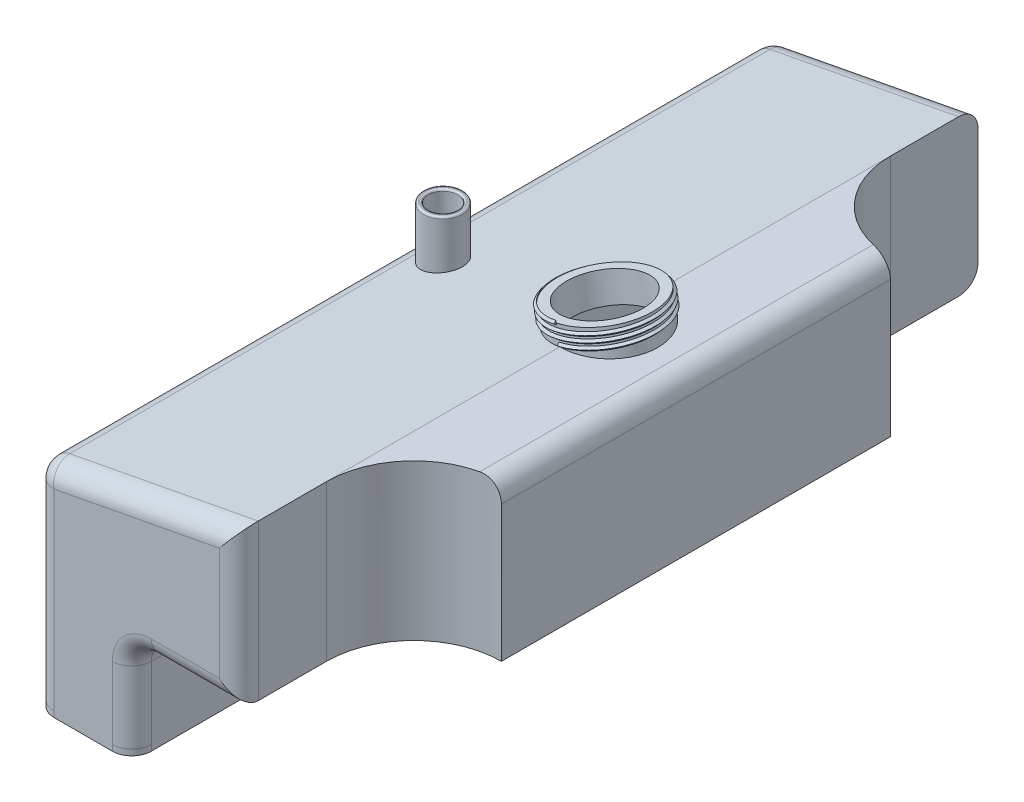
SolidWorks part; units mm, degrees
ref_plane "Front Plane" through (0, 0, 0) normal (0, 0, 1) x (1, 0, 0)
ref_plane "Top Plane" through (0, 0, 0) normal (0, 1, 0) x (1, 0, 0)
ref_plane "Right Plane" through (0, 0, 0) normal (1, 0, 0) x (0, 0, -1)
sketch "Sketch1" plane through (0, 0, 0) normal (0, 1, 0) x (1, 0, 0)
  line L0 (0, 0) -> (0, -145) construction
  line L5 (0, 0) -> (0, 145) construction
  line L6 (0, 100) -> (0, -100)
  line L8 (-150, -145) -> (-150, 145)
  line L12 (-150, 145) -> (-150, 190)
  line L13 (-150, 190) -> (-45, 190)
  line L14 (-45, 145) -> (-45, 190)
  line L16 (-150, -145) -> (-150, -190)
  line L17 (-150, -190) -> (-45, -190)
  line L18 (-45, -145) -> (-45, -190)
  arc A2 (-45, 145) -> (0, 100) centre (0, 145) ccw
  arc A3 (0, -100) -> (-45, -145) centre (0, -145) ccw
extrude "Boss-Extrude4" add sketch "Sketch1" along normal blind 80
sketch "Sketch2" plane through (0, 0, 0) normal (0, -1, 0) x (1, 0, 0)
  line L0 (-45, -190) -> (-150, -190) construction
  line L1 (-150, 190) -> (-100, 190)
  line L2 (-150, 190) -> (-150, -190)
  line L3 (-150, -190) -> (-100, -190)
  line L4 (-100, 190) -> (-100, -190)
extrude "Boss-Extrude5" add sketch "Sketch2" along normal blind 50
sketch "Sketch4" plane through (0, 0, 190) normal (0, 0, 1) x (1, 0, 0)
  line L0 (-45, 80) -> (-45, 60) construction
  line L1 (-45, 80) -> (-45, 0) construction
  line L2 (-45, 60) -> (-150, 60) construction
  line L3 (-150, 80) -> (-150, -50) construction
  line L4 (-150, 60) -> (-45, 80)
  line L5 (-150, 80) -> (-150, 60)
  line L6 (-150, 80) -> (-45, 80)
extrude "Cut-Extrude2" cut sketch "Sketch4" against normal through all
fillet "Fillet1" radius 10 11 edges at (-100, -25, -190) (-72.5, 0, 190) (-150, 5, -190) (-72.5, 0, -190) (-100, -25, 190) (-100, 0, 0) (-150, 5, 190) (-45, 40, 190) (-97.5, 70, -190) (-97.5, 70, 190) (-150, 60, 0)
fillet "Fillet2" radius 10 1 edges at (0, 80, 0)
shell "Shell1" thickness 5 removed face at (-125, -50, 0)
sketch "Sketch5" plane through (0, 0, -185) normal (0, 0, 1) x (1, 0, 0)
  line L0 (-100, -10) -> (-100, -50) construction
  line L1 (-150, -50) -> (-100, -50)
  line L2 (-150, -50) -> (-150, -47)
  line L3 (-150, -47) -> (-100, -47)
  line L4 (-100, -50) -> (-100, -47)
extrude "Boss-Extrude6" add sketch "Sketch5" along normal through all
fillet "Fillet3" radius 10 4 edges at (-150, -48.5, -185) (-100, -48.5, -185) (-100, -48.5, 190) (-150, -48.5, 190)
sketch "Sketch6" plane through (-16.2801, 85.4705, 0) normal (-0.1871, 0.9823, 0) x (0.9823, 0.1871, 0)
  line L0 (-29.2363, -145) -> (-29.2363, 145) construction
  circle A0 centre (-29.2363, 0) radius 20
  circle A1 centre (-29.2363, 0) radius 25
extrude "Boss-Extrude7" add sketch "Sketch6" along normal blind 10 and the other way blind 5
sketch "Sketch7" plane through (-18.1512, 95.2938, 0) normal (-0.1871, 0.9823, 0) x (0.9823, 0.1871, 0)
  line L0 (-29.2363, -20) -> (-29.2363, 20) construction
  circle A0 centre (-29.2363, 0) radius 25
curve "Helix/Spiral1" pitch 3 height 9 radius 25 centre (-46.8711, 89.8234, 0) axis (0.1871, -0.9823, 0) start towards (0, 0, 1)
ref_plane "Plane1" through (-28.7199, -5.4705, 0) normal (0.9823, 0.1871, 0) x (0, 0, -1)
sketch "Sketch8" plane through (-28.7199, -5.4705, 0) normal (0.9823, 0.1871, 0) x (0, 0, -1)
  line L0 (-25, 89.0071) -> (-25, 87.0071)
  line L1 (-25, 97.0071) -> (-25, 87.0071) construction
  line L2 (-25, 87.0071) -> (-26.203, 88.0071)
  line L4 (-25, 89.0071) -> (-26.203, 88.0071)
  spline S0 degree 3 poles (-25, 97.0071) (-25, 96.9618) (-24.3156, 96.8707) (-21.3192, 96.7344) (-16.5956, 96.598) (-10.5275, 96.4617) (-3.6066, 96.3253) (3.6066, 96.1889) (10.5275, 96.0526) (16.5956, 95.9162) (21.3192, 95.7799) (24.3156, 95.6435) (25.3422, 95.5071) (24.3156, 95.3708) (21.3192, 95.2344) (16.5956, 95.098) (10.5275, 94.9617) (3.6066, 94.8253) (-3.6066, 94.6889) (-10.5275, 94.5526) (-16.5956, 94.4162) (-21.3192, 94.2799) (-24.3156, 94.1435) (-25.3422, 94.0071) (-24.3156, 93.8708) (-21.3192, 93.7344) (-16.5956, 93.598) (-10.5275, 93.4617) (-3.6066, 93.3253) (3.6066, 93.1889) (10.5275, 93.0526) (16.5956, 92.9162) (21.3192, 92.7799) (24.3156, 92.6435) (25.3422, 92.5071) (24.3156, 92.3708) (21.3192, 92.2344) (16.5956, 92.098) (10.5275, 91.9617) (3.6066, 91.8253) (-3.6066, 91.6889) (-10.5275, 91.5526) (-16.5956, 91.4162) (-21.3192, 91.2799) (-24.3156, 91.1435) (-25.3422, 91.0071) (-24.3156, 90.8708) (-21.3192, 90.7344) (-16.5956, 90.598) (-10.5275, 90.4617) (-3.6066, 90.3253) (3.6066, 90.1889) (10.5275, 90.0526) (16.5956, 89.9162) (21.3192, 89.7799) (24.3156, 89.6435) (25.3422, 89.5071) (24.3156, 89.3708) (21.3192, 89.2344) (16.5956, 89.098) (10.5275, 88.9617) (3.6066, 88.8253) (-3.6066, 88.6889) (-10.5275, 88.5526) (-16.5956, 88.4162) (-21.3192, 88.2798) (-24.3156, 88.1436) (-25, 88.0524) (-25, 88.0071) knots 0 0 0 0 0.015152 0.030303 0.045455 0.060606 0.075758 0.090909 0.106061 0.121212 0.136364 0.151515 0.166667 0.181818 0.19697 0.212121 0.227273 0.242424 0.257576 0.272727 0.287879 0.30303 0.318182 0.333333 0.348485 0.363636 0.378788 0.393939 0.409091 0.424242 0.439394 0.454545 0.469697 0.484848 0.5 0.515152 0.530303 0.545455 0.560606 0.575758 0.590909 0.606061 0.621212 0.636364 0.651515 0.666667 0.681818 0.69697 0.712121 0.727273 0.742424 0.757576 0.772727 0.787879 0.80303 0.818182 0.833333 0.848485 0.863636 0.878788 0.893939 0.909091 0.924242 0.939394 0.954545 0.969697 0.984848 1 1 1 1 construction
  point P10 (-25, 88.0071)
sweep "Sweep1" add profiles "Sketch8" path "Helix/Spiral1"
sketch "Sketch9" plane through (-18.1512, 95.2938, 0) normal (-0.1871, 0.9823, 0) x (0.9823, 0.1871, 0)
  circle A0 centre (-29.2363, 0) radius 20
extrude "Cut-Extrude3" cut sketch "Sketch9" against normal up to next
ref_plane "Plane2" through (0, 80, 0) normal (0, 1, 0) x (1, 0, 0)
sketch "Sketch10" plane through (0, 80, 0) normal (0, 1, 0) x (1, 0, 0)
  line L0 (-150, 0) -> (-130, 0) construction
  line L1 (-150, -180) -> (-150, 180) construction
  circle A0 centre (-130, 0) radius 10
  circle A1 centre (-130, 0) radius 7.5
extrude "Boss-Extrude8" add sketch "Sketch10" against normal blind 120 and the other way blind 10 separate body
fillet "Fillet4" radius 1 2 edges at (-130, 90, 7.5) (-130, 90, 10)
sketch "Sketch11" plane through (0, 90, 0) normal (0, 1, 0) x (1, 0, 0)
  circle A0 centre (-130, 0) radius 7.5
extrude "Cut-Extrude4" cut sketch "Sketch11" against normal blind 120
sketch "Sketch12" plane through (0, 0, 0) normal (0, 0, 1) x (1, 0, 0)
  line L4 (-119.5137, -23.124) -> (-119.5137, -40.5094)
  line L8 (-119.5137, -40.5094) -> (-140.7965, -40.5094)
  line L9 (-140.7965, -40.5094) -> (-119.5137, -23.124)
extrude "Cut-Extrude7" cut sketch "Sketch12" against normal blind 12 and the other way blind 12
